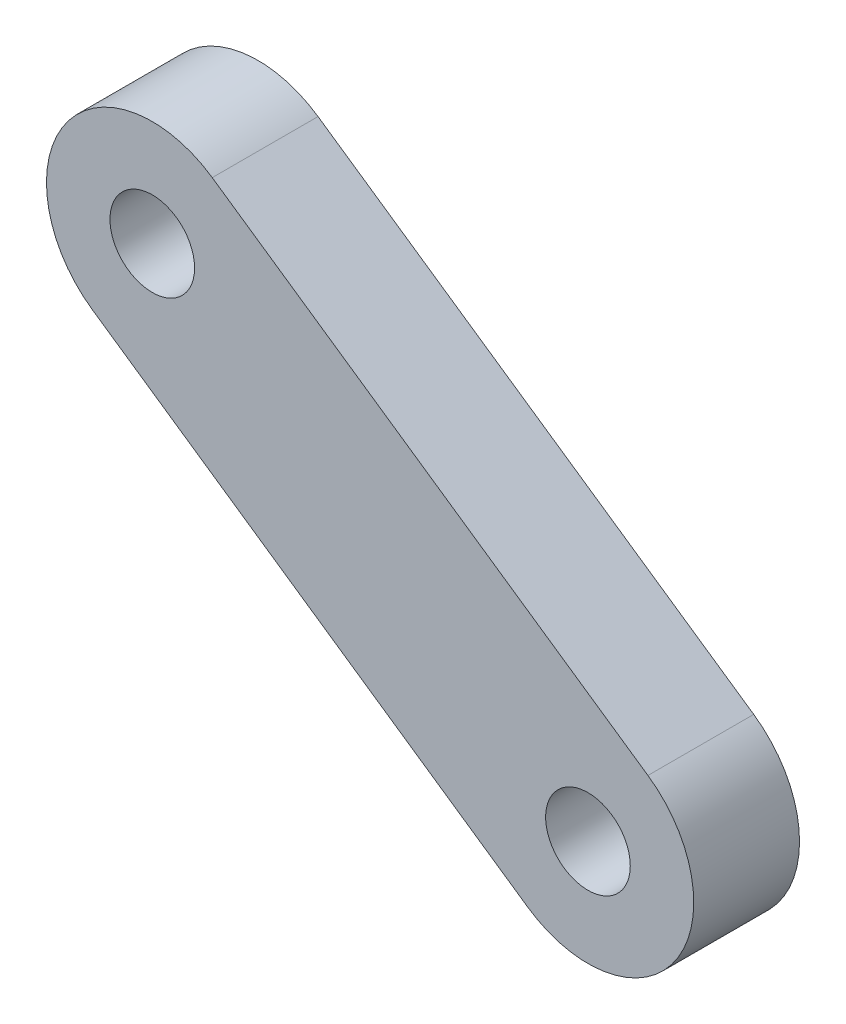
SolidWorks part; units mm, degrees
ref_plane "Front Plane" through (0, 0, 0) normal (0, 0, 1) x (1, 0, 0)
ref_plane "Top Plane" through (0, 0, 0) normal (0, 1, 0) x (1, 0, 0)
ref_plane "Right Plane" through (0, 0, 0) normal (1, 0, 0) x (0, 0, -1)
sketch "Sketch1" plane through (0, 0, 0) normal (0, 0, 1) x (0.9998, -0.022, 0)
  line L0 (0.6447, 52.8572) -> (-25.8837, 70.342) construction
  line L1 (5.01, 49.98) -> (5.01, 69.98) construction
  line L2 (5.01, 69.98) -> (-55.6789, 69.98) construction
  line L3 (-46.2352, 83.6971) -> (-25.3345, 69.98) construction
  line L4 (-46.2352, 83.6971) -> (-43.4918, 87.8772) construction
  line L5 (-43.4918, 87.8772) -> (-48.9786, 79.5169) construction
  line L6 (-43.4918, 87.8772) -> (-22.591, 74.1602)
  line L7 (-48.9786, 79.5169) -> (-28.0779, 65.7999)
  line L8 (-22.591, 74.1602) -> (-28.0779, 65.7999) construction
  circle A0 centre (5.01, 49.98) radius 2 construction
  circle A1 centre (5.01, 49.98) radius 2 construction
  circle A3 centre (-25.3345, 69.98) radius 2
  arc A4 (-29.5092, 72.7316) -> (-29.5146, 72.7234) centre (-25.3345, 69.98) ccw
  circle A5 centre (-46.2352, 83.6971) radius 2 construction
  circle A6 centre (-46.2352, 83.6971) radius 2
  arc A7 (-43.4918, 87.8772) -> (-48.9786, 79.5169) centre (-46.2352, 83.6971) ccw
  arc A8 (-28.0779, 65.7999) -> (-22.591, 74.1602) centre (-25.3345, 69.98) ccw
  point P18 (-25.3345, 69.98)
  dimension "D1" = 5
  dimension "D2" = 5
  dimension "D4" = 4
  dimension "D5" = 4
  dimension "D6" = 10
  dimension "D3" = 20
  dimension "D7" = 25
extrude "Boss-Extrude1" add sketch "Sketch1" along normal blind 5 contours L7 A8 L6 A7 A3 A6 region at (-34.0834, 77.6083, 0)
